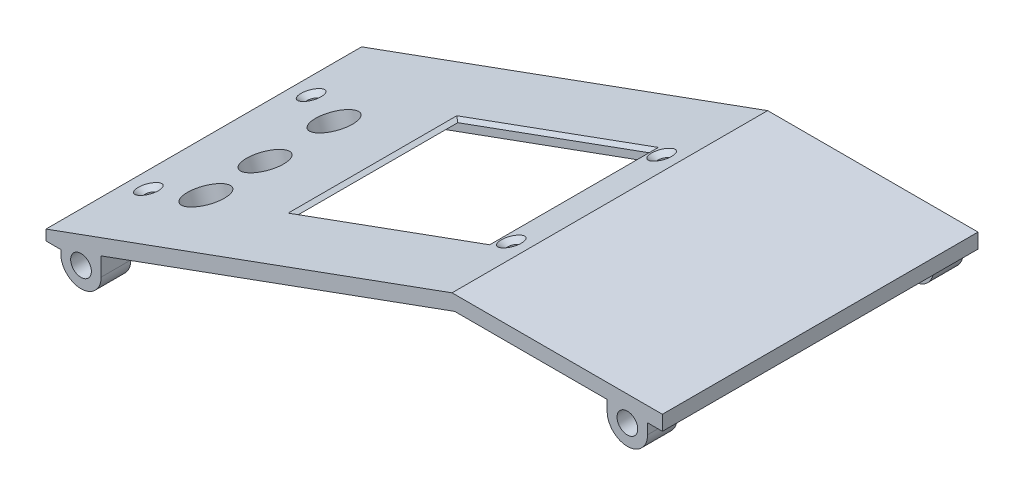
SolidWorks part; units mm, degrees
ref_plane "Спереди" through (0, 0, 0) normal (0, 0, 1) x (1, 0, 0)
ref_plane "Сверху" through (0, 0, 0) normal (0, 1, 0) x (1, 0, 0)
ref_plane "Справа" through (0, 0, 0) normal (1, 0, 0) x (0, 0, -1)
sketch "Эскиз1" plane through (0, 0, 0) normal (0, 0, 1) x (1, 0, 0)
  line L0 (11.6239, 71) -> (10.5978, 73.8191) construction
  line L1 (53.75, 74) -> (11.0949, 74)
  line L2 (11.0949, 74) -> (-71.25, 44.0289)
  line L3 (-71.25, 44.0289) -> (-71.25, 41.9283)
  line L4 (-71.25, 41.9283) -> (-68.25, 41.9283)
  line L5 (-68.25, 41.9283) -> (11.6239, 71)
  line L6 (11.6239, 71) -> (53.75, 71)
  line L7 (53.75, 71) -> (53.75, 74)
  line L8 (-68.25, 41.9283) -> (-69.2761, 44.7474) construction
  line L10 (53.75, -6) -> (53.75, 71) construction
  line L11 (53.75, 71) -> (50.75, 71) construction
  line L12 (-71.25, 41.9283) -> (-71.25, -6) construction
  dimension "D1" = 3
  dimension "D2" = 20
  dimension "D3" = 85
extrude "Бобышка-Вытянуть1" add sketch "Эскиз1" along normal mid plane 64
sketch "Эскиз2" plane through (0, 0, 0) normal (0, 0, 1) x (1, 0, 0)
  line L2 (42.55, 74) -> (42.55, 68.9)
  line L4 (50.75, 71) -> (50.75, 3.2) construction
  line L5 (50.75, 68.9) -> (50.75, 74)
  line L6 (53.75, 74) -> (11.0949, 74) construction
  line L7 (50.75, 74) -> (42.55, 74)
  line L9 (-60.05, 48.1054) -> (-60.05, 41.1858)
  line L10 (11.0949, 74) -> (-71.25, 44.0289) construction
  line L11 (-68.25, -3) -> (-68.25, 41.9283) construction
  line L12 (-68.25, 41.1858) -> (-68.25, 45.1208)
  line L13 (-68.25, 45.1208) -> (-60.05, 48.1054)
  arc A0 (42.55, 68.9) -> (50.75, 68.9) centre (46.65, 68.9) ccw
  circle A1 centre (46.65, 68.9) radius 2.1
  arc A2 (-60.05, 41.1858) -> (-68.25, 41.1858) centre (-64.15, 41.1858) cw
  circle A3 centre (-64.15, 41.1858) radius 2.1
  dimension "D1" = 4.2
  dimension "D2" = 2
  dimension "D3" = 3
  dimension "D4" = 2
  dimension "D5" = 3
extrude "Бобышка-Вытянуть2" add sketch "Эскиз2" against normal blind 6 from surface contours L2 A0 L5 L7 A1 | A1 | A2 L9 L13 L12 A3 | A3 region at (46.65, 73.8768, 0) region at (-60.1874, 44.6456, 0) region at (46.65, 68.9, 0) region at (-64.15, 41.1858, 0) starting at face at (-11.5045, 59.6979, 32)
extrude "Бобышка-Вытянуть3" add sketch "Эскиз2<3>" along normal blind 6 from surface contours A1 | L2 A0 L5 L7 A1 | A2 L9 L13 L12 A3 | A3 region at (46.65, 73.8768, 0) region at (-60.1874, 44.6456, 0) region at (46.65, 68.9, 0) region at (-64.15, 41.1858, 0) starting at face at (-11.5045, 59.6979, -32)
sketch "Эскиз2<3>" plane through (0, 0, 0) normal (0, 0, 1) x (1, 0, 0) same geometry as "Эскиз2"
extrude "Вырез-Вытянуть1" cut sketch "Эскиз2<4>" against normal blind 4 from surface contours A1 | A3 region at (46.65, 68.9, 0) region at (-64.15, 41.1858, 0) starting at face at (-5.8772, 58.3407, 32)
sketch "Эскиз2<4>" plane through (0, 0, 0) normal (0, 0, 1) x (1, 0, 0) same geometry as "Эскиз2"
extrude "Вырез-Вытянуть2" cut sketch "Эскиз2<5>" along normal blind 4 from surface contours A1 | A3 region at (46.65, 68.9, 0) region at (-64.15, 41.1858, 0) starting at face at (-5.8772, 58.3407, -32)
sketch "Эскиз2<5>" plane through (0, 0, 0) normal (0, 0, 1) x (1, 0, 0) same geometry as "Эскиз2"
sketch "Эскиз3" plane through (-21.4592, 58.9587, 0) normal (0.342, -0.9397, 0) x (0.9397, 0.342, 0)
  line L8 (-20.2937, -17.8) -> (-20.2937, -14.8)
  line L9 (28.7063, -17.8) -> (-20.2937, -17.8)
  line L10 (28.7063, 17.8) -> (28.7063, -17.8)
  line L11 (-19.7937, 17.8) -> (28.7063, 17.8)
  line L12 (-20.2937, -17.8) -> (-20.2937, 17.8)
  line L13 (28.7063, -17.8) -> (-20.2937, -17.8)
  line L14 (28.7063, 17.8) -> (28.7063, -17.8)
  line L15 (-20.2937, 17.8) -> (28.7063, 17.8)
  dimension "D1" = 0.5
extrude "Вырез-Вытянуть3" cut sketch "Эскиз3" against normal blind 2.3
sketch "Эскиз4" plane through (-21.4592, 58.9587, 0) normal (0.342, -0.9397, 0) x (0.9397, 0.342, 0)
  line L16 (-14.7937, -16.4) -> (27.3063, -16.4)
  line L17 (-14.7937, 16.4) -> (-14.7937, -16.4)
  line L18 (27.3063, 16.4) -> (-14.7937, 16.4)
  line L19 (27.3063, -16.4) -> (27.3063, 16.4)
  line L20 (-14.7937, -16.4) -> (27.3063, -16.4)
  line L21 (-14.7937, 16.4) -> (-14.7937, -16.4)
  line L22 (27.3063, 16.4) -> (-14.7937, 16.4)
  line L23 (27.3063, -16.4) -> (27.3063, 16.4)
  dimension "D1" = 0.5
extrude "Вырез-Вытянуть4" cut sketch "Эскиз4" against normal through all
chamfer "Фаска1" distance 0.7 angle 45 4 edges at (3.1742, 71.1171, 0) (-36.3868, 56.7181, 0) (-16.6063, 63.9176, -16.4) (-16.6063, 63.9176, 16.4)
hole_wizard "Зенковка для винта с потайной головкой M21" positions "Эскиз5" profile "Эскиз6" countersink size "M2" standard "DIN" end condition through all
sketch "Эскиз5" plane through (-22.4853, 61.7778, 0) normal (-0.342, 0.9397, 0) x (0.9397, 0.342, 0)
  point P0 (30.7083, 15.22)
  point P6 (-46.2937, 16.5)
  point P9 (-46.2937, -16.5)
  point P15 (30.7083, -15.26)
sketch "Эскиз6" plane through (6.3711, 72.2807, -15.22) normal (0, 0, 1) x (-0.9397, -0.342, 0)
  line L0 (0, 0) -> (0, 49.2769)
  line L1 (0, 49.2769) -> (1.2, 49.2769)
  line L2 (1.2, 49.2769) -> (1.2, 1)
  line L3 (1.2, 1) -> (2.2, 0)
  line L5 (2.2, 0) -> (0, 0)
  line L6 (-1.2, 1) -> (-2.2, 0) construction
  line L11 (0, -6.35) -> (0, 107.95) construction
  dimension "Диаметр сквозного отверстия" = 2.4
  dimension "Глубина сквозного отверстия" = 49.2769
  dimension "Диаметр передней зенковки" = 4.4
  dimension "Угол передней зенковки" = 90
sketch "Эскиз7" plane through (-22.4853, 61.7778, 0) normal (-0.342, 0.9397, 0) x (0.9397, 0.342, 0)
  circle A2 centre (-34.6937, 10.25) radius 4
  circle A3 centre (-34.6937, 10.25) radius 4
  circle A20 centre (-34.6787, -3.75) radius 4
  circle A21 centre (-34.6787, -15.75) radius 4
  dimension "D2" = 8
  dimension "D1" = 0.5
extrude "Вырез-Вытянуть5" cut sketch "Эскиз7" against normal blind 10
